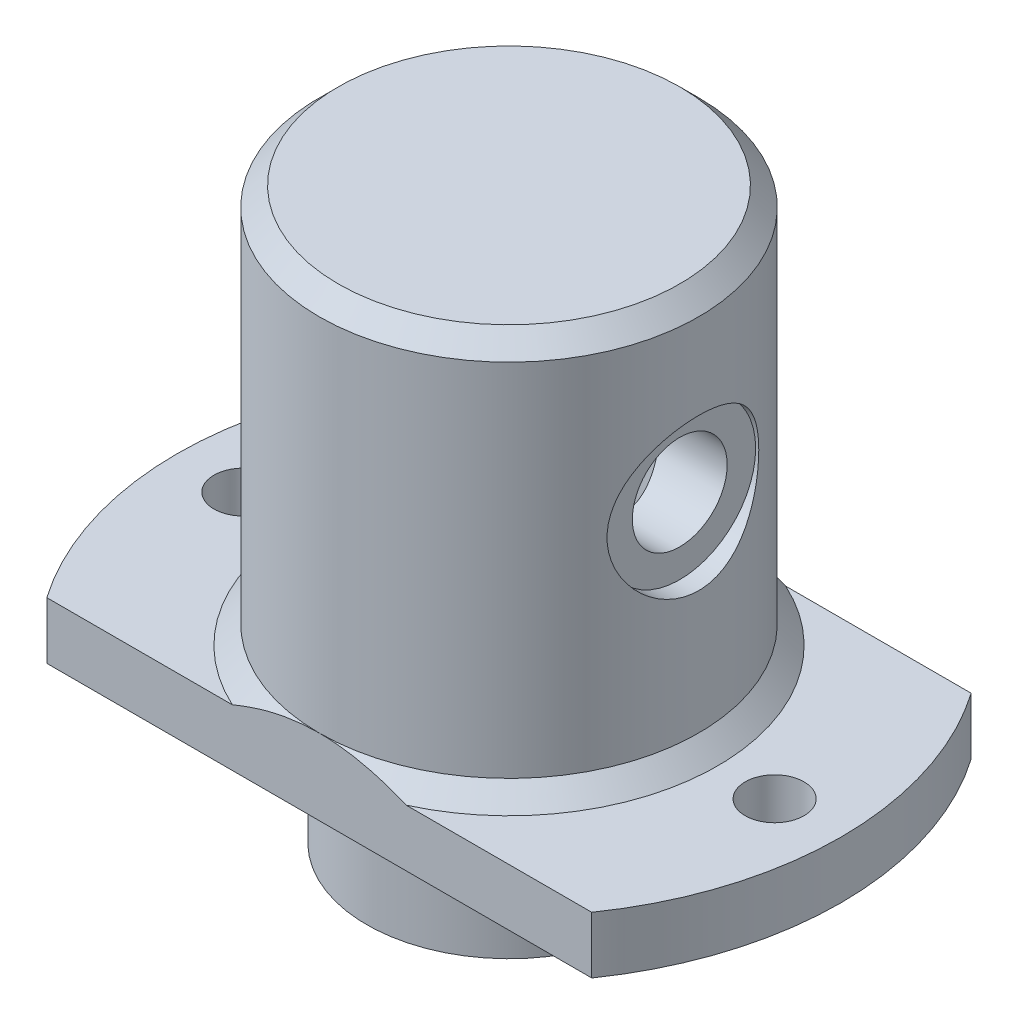
SolidWorks part; units mm, degrees
ref_plane "Front Plane" through (0, 0, 0) normal (0, 0, 1) x (1, 0, 0)
ref_plane "Top Plane" through (0, 0, 0) normal (0, 1, 0) x (1, 0, 0)
ref_plane "Right Plane" through (0, 0, 0) normal (1, 0, 0) x (0, 0, -1)
sketch "Sketch1" plane through (0, 0, 0) normal (0, 1, 0) x (1, 0, 0)
  circle A0 centre (0, 0) radius 10
extrude "Boss-Extrude1" add sketch "Sketch1" along normal blind 21
sketch "Sketch2" plane through (0, 0, 0) normal (0, -1, 0) x (1, 0, 0)
  line L1 (-14.3614, -10) -> (14.3614, -10)
  line L3 (-14.3614, 10) -> (14.3614, 10)
  line L5 (-16.4829, -5.879) -> (16.4829, 5.879) construction
  line L6 (-16.4829, 5.879) -> (16.4829, -5.879) construction
  arc A0 (14.3614, -10) -> (14.3614, 10) centre (0, 0) ccw
  arc A1 (-14.3614, 10) -> (-14.3614, -10) centre (0, 0) ccw
  circle A2 centre (-14, 0) radius 1.55
  circle A3 centre (14, 0) radius 1.55
  dimension "D1" = 3.1
  dimension "D2" = 3.1
  dimension "D3" = 14
  dimension "D4" = 14
extrude "Boss-Extrude2" add sketch "Sketch2" along normal blind 3
sketch "Sketch3" plane through (0, -3, 0) normal (0, -1, 0) x (1, 0, 0)
  circle A0 centre (0, 0) radius 7.5
extrude "Boss-Extrude3" add sketch "Sketch3" along normal blind 6
sketch "Sketch4" plane through (0, -9, 0) normal (0, -1, 0) x (1, 0, 0)
  circle A0 centre (0, 0) radius 6
extrude "Cut-Extrude1" cut sketch "Sketch4" against normal blind 25
ref_plane "Plane1" through (10, 0, 0) normal (1, 0, 0) x (0, 0, -1)
sketch "Sketch6" plane through (10, 0, 0) normal (1, 0, 0) x (0, 0, -1)
  line L0 (-7.5, -9) -> (7.5, -9) construction
  circle A0 centre (0, 11.5) radius 4
  dimension "D1" = 8
  dimension "D2" = 20.5
extrude "Cut-Extrude2" cut sketch "Sketch6" against normal blind 1
sketch "Sketch7" plane through (9, 0, 0) normal (1, 0, 0) x (0, 0, -1)
  circle A0 centre (0, 11.5) radius 2.5
extrude "Cut-Extrude3" cut sketch "Sketch7" against normal blind 6
chamfer "Chamfer1" distance 1 angle 45 3 edges at (10, 0, 0) (0, 21, 10) (-10, 0, 0)
